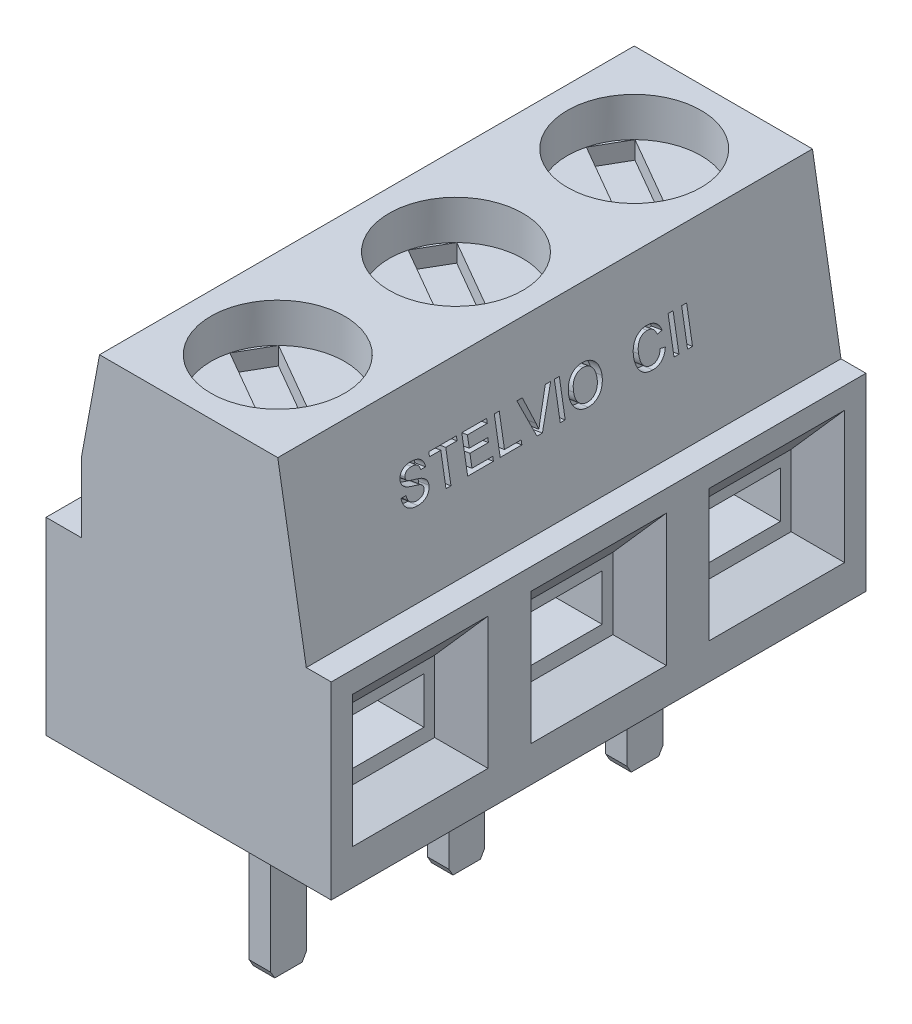
SolidWorks part; units mm, degrees
ref_plane "X Y" through (0, 0, 0) normal (0, 0, 1) x (1, 0, 0)
ref_plane "X -Z" through (0, 0, 0) normal (0, 1, 0) x (1, 0, 0)
ref_plane "-Z Y" through (0, 0, 0) normal (1, 0, 0) x (0, 0, -1)
sketch "Skica1" plane through (0, 0, 0) normal (0, 0, 1) x (1, 0, 0)
  line L0 (-2.5, 10) -> (2.5, 10)
  line L1 (2.5, 10) -> (3.3, 5.3)
  line L2 (3.3, 5.3) -> (4, 5.3)
  line L3 (4, 5.3) -> (4, 0)
  line L4 (4, 0) -> (-4, 0)
  line L5 (-4, 0) -> (-4, 5.3)
  line L6 (-4, 5.3) -> (-3, 5.3)
  line L7 (-3, 5.3) -> (-3, 7.3)
  line L8 (-3, 7.3) -> (-2.5, 10)
  dimension "D1" = 10
  dimension "D2" = 0.7
  dimension "D3" = 1
  dimension "D4" = 8
  dimension "D5" = 5.3
  dimension "D6" = 5.3
  dimension "D7" = 2
  dimension "D8" = 1.5
  dimension "D9" = 5
extrude "Základ-Protažení" add sketch "Skica1" along normal blind 15
sketch "Skica2" plane through (0, 10, 0) normal (0, 1, 0) x (-1, 0, 0)
  line L0 (-2.5, 0) -> (2.5, 0) construction
  line L1 (2.5, 15) -> (2.5, 0) construction
  line L2 (-2.5, 15) -> (2.5, 15) construction
  circle A0 centre (0, 2.5) radius 1.875
  circle A1 centre (0, 7.5) radius 1.875
  circle A2 centre (0, 12.5) radius 1.875
  dimension "D1" = 3.75
  dimension "D5" = 2.5
  dimension "D2" = 2.5
  dimension "D3" = 2.5
  dimension "D4" = 5
extrude "Odebrání-Protažení1" cut sketch "Skica2" against normal blind 1.1
sketch "Skica3" plane through (0, 8.9, 0) normal (0, 1, 0) x (-1, 0, 0)
  line L0 (1.815, 2.0295) -> (-1.315, 3.8366)
  line L1 (1.815, 2.0295) -> (1.315, 1.1634)
  line L2 (-1.315, 3.8366) -> (-1.815, 2.9705)
  line L3 (1.315, 1.1634) -> (-1.815, 2.9705)
  line L4 (-2.5, 0) -> (2.5, 0) construction
  line L5 (1.815, 7.0295) -> (-1.315, 8.8366)
  line L6 (1.815, 7.0295) -> (1.315, 6.1634)
  line L7 (1.315, 6.1634) -> (-1.815, 7.9705)
  line L8 (-1.315, 8.8366) -> (-1.815, 7.9705)
  line L9 (1.815, 12.0295) -> (-1.315, 13.8366)
  line L10 (1.815, 12.0295) -> (1.315, 11.1634)
  line L11 (1.315, 11.1634) -> (-1.815, 12.9705)
  line L12 (-1.315, 13.8366) -> (-1.815, 12.9705)
  line L13 (-2.5, 15) -> (2.5, 15) construction
  circle A0 centre (0, 2.5) radius 1.875 construction
  dimension "D1" = 1
  dimension "D2" = 30
  dimension "D3" = 2.9705
  dimension "D4" = 4.3301
extrude "Odebrání-Protažení2" cut sketch "Skica3" against normal blind 0.5
sketch "Skica4" plane through (-4, 0, 0) normal (-1, 0, 0) x (0, 0, 1)
  line L0 (15, 5.3) -> (0, 5.3) construction
  line L1 (13.55, 5.3) -> (11.45, 5.3)
  line L2 (13.55, 5.3) -> (13.55, 2.3)
  line L3 (13.55, 2.3) -> (11.45, 2.3)
  line L4 (11.45, 5.3) -> (11.45, 2.3)
  line L5 (15, 0) -> (0, 0) construction
  line L6 (13.1, 0) -> (11.9, 0)
  line L7 (13.1, 0) -> (13.1, 1)
  line L8 (13.1, 1) -> (11.9, 1)
  line L9 (11.9, 0) -> (11.9, 1)
  line L10 (15, 5.3) -> (15, 0) construction
  line L11 (8.55, 5.3) -> (6.45, 5.3)
  line L12 (8.55, 5.3) -> (8.55, 2.3)
  line L13 (8.55, 2.3) -> (6.45, 2.3)
  line L14 (6.45, 5.3) -> (6.45, 2.3)
  line L15 (8.1, 0) -> (6.9, 0)
  line L16 (8.1, 0) -> (8.1, 1)
  line L17 (8.1, 1) -> (6.9, 1)
  line L18 (6.9, 0) -> (6.9, 1)
  line L19 (3.55, 5.3) -> (1.45, 5.3)
  line L20 (3.55, 5.3) -> (3.55, 2.3)
  line L21 (3.55, 2.3) -> (1.45, 2.3)
  line L22 (1.45, 5.3) -> (1.45, 2.3)
  line L23 (3.1, 0) -> (1.9, 0)
  line L24 (3.1, 0) -> (3.1, 1)
  line L25 (3.1, 1) -> (1.9, 1)
  line L26 (1.9, 0) -> (1.9, 1)
  line L27 (15, 10) -> (0, 10) construction
  dimension "D1" = 2.1
  dimension "D2" = 1.45
  dimension "D3" = 3
  dimension "D4" = 1.2
  dimension "D5" = 0.45
  dimension "D6" = 1
  dimension "D7" = 2.9
  dimension "D8" = 4.7
extrude "Odebrání-Protažení3" cut sketch "Skica4" against normal blind 0.5
sketch "Skica5" plane through (4, 0, 0) normal (1, 0, 0) x (0, 0, -1)
  line L0 (-15, 0) -> (0, 0) construction
  line L1 (-13.9, 3.5) -> (-11.1, 3.5)
  line L2 (-13.9, 3.5) -> (-13.9, 1.5)
  line L3 (-13.9, 1.5) -> (-11.1, 1.5)
  line L4 (-11.1, 3.5) -> (-11.1, 1.5)
  line L5 (-15, 0) -> (-15, 5.3) construction
  dimension "D1" = 2.8
  dimension "D2" = 2
  dimension "D3" = 1.5
  dimension "D4" = 1.1
extrude "Odebrání-Protažení4" cut sketch "Skica5" against normal blind 1
pattern_linear "Lineární Pole1" count 3 spacing 5 along (0, 0, -1) of "Odebrání-Protažení4"
chamfer "Zkosení1" distance 1.2 distance2 1 3 edges at (4, 3.5, 12.5) (4, 3.5, 2.5) (4, 3.5, 7.5) first distance on face at (4, 2.5, 7.5)
chamfer "Zkosení2" distance 0.5 distance2 1 9 edges at (4, 3.1, 11.1) (4, 1.5, 12.5) (4, 3.1, 13.9) (4, 3.1, 1.1) (4, 1.5, 2.5) (4, 3.1, 3.9) (4, 3.1, 6.1) (4, 1.5, 7.5) (4, 3.1, 8.9) first distance on face at (4, 3.1, 7.5)
sketch "Skica6" plane through (3, 0, 0) normal (1, 0, 0) x (0, 0, -1)
  line L0 (-11.1, 3.5) -> (-13.9, 3.5) construction
  line L1 (-13.5, 3.2) -> (-11.4, 3.2)
  line L2 (-13.5, 3.2) -> (-13.5, 1.9)
  line L3 (-13.5, 1.9) -> (-11.4, 1.9)
  line L4 (-11.4, 3.2) -> (-11.4, 1.9)
  line L6 (-11.1, 1.5) -> (-11.1, 3.5) construction
  dimension "D1" = 1.3
  dimension "D2" = 2.1
  dimension "D4" = 0.3
  dimension "D6" = 0.3
extrude "Odebrání-Protažení5" cut sketch "Skica6" against normal blind 2
pattern_linear "Lineární Pole2" count 3 spacing 5 along (0, 0, -1) of "Odebrání-Protažení5"
sketch "Skica7" plane through (0, 0, 0) normal (0, -1, 0) x (1, 0, 0)
  line L0 (-4, 0) -> (4, 0) construction
  line L1 (-0.3, 2) -> (0.3, 2)
  line L2 (-0.3, 2) -> (-0.3, 3)
  line L3 (-0.3, 3) -> (0.3, 3)
  line L4 (0.3, 2) -> (0.3, 3)
  line L5 (-4, 1.9) -> (-4, 0) construction
  dimension "D1" = 0.6
  dimension "D2" = 1
  dimension "D3" = 2
  dimension "D4" = 3.7
extrude "Přidání-Protažení1" add sketch "Skica7" along normal blind 4.8
pattern_linear "Lineární Pole3" count 3 spacing 5 along (0, 0, 1) of "Přidání-Protažení1"
chamfer "Zkosení3" distance 0.2 angle 30 6 edges at (0, -4.8, 3) (0, -4.8, 2) (0, -4.8, 13) (0, -4.8, 12) (0, -4.8, 8) (0, -4.8, 7) first distance on face at (0, -2.4, 3) first distance on face at (0, -2.4, 2) first distance on face at (0, -2.4, 13) first distance on face at (0, -2.4, 12) first distance on face at (0, -2.4, 8) first distance on face at (0, -2.4, 7)
sketch "Skica9" plane through (4.0838, 0.6951, 0) normal (0.9858, 0.1678, 0) x (0, 0, -1)
  line L0 (-15, 9.4387) -> (0, 9.4387) construction
  line L1 (-15, 4.6711) -> (-15, 9.4387) construction
  text T0 "STELVIO  CII\r\n" font "Arial" height 1
  dimension "D1" = 2.7
  dimension "D2" = 3
extrude "Odebrání-Protažení6" cut sketch "Skica9" against normal blind 0.3
sketch "Sketch1" plane through (0, 0, 0) normal (0, -1, 0) x (1, 0, 0)
  line L0 (-0.3, 7.5) -> (0.3, 7.5) construction
  line L1 (-0.3, 7.8845) -> (-0.3, 7.1155) construction
  line L2 (0.3, 7.1155) -> (0.3, 7.8845) construction
  circle A0 centre (0, 7.5) radius 0.7131
  dimension "D1" = 1.4261
